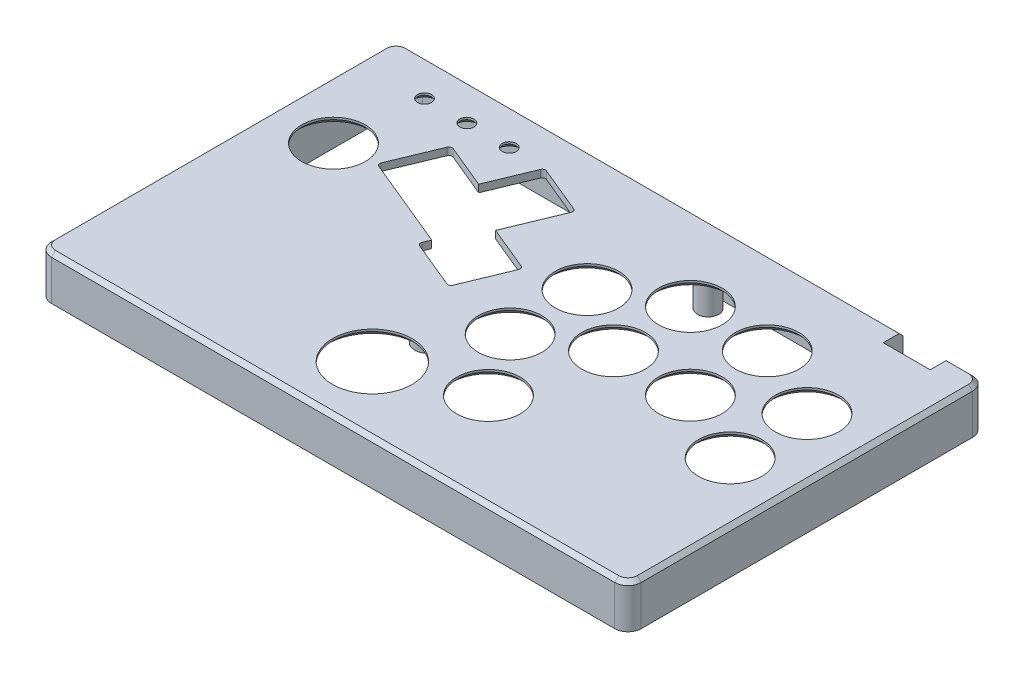
SolidWorks part; units mm, degrees
ref_plane "Front Plane" through (0, 0, 0) normal (0, 0, 1) x (1, 0, 0)
ref_plane "Top Plane" through (0, 0, 0) normal (0, 1, 0) x (1, 0, 0)
ref_plane "Right Plane" through (0, 0, 0) normal (1, 0, 0) x (0, 0, -1)
sketch "Sketch1" plane through (0, 0, 0) normal (0, 1, 0) x (1, 0, 0)
  line L1 (0, 0) -> (222.53, 0)
  line L2 (0, 0) -> (0, 135)
  line L3 (0, 135) -> (222.53, 135)
  line L4 (222.53, 0) -> (222.53, 135)
  dimension "D1" = 222.53
  dimension "D2" = 135
extrude "Top Plate" add sketch "Sketch1" along normal blind 16.6
fillet "Corner Fillet" radius 5 4 edges at (0, 8.3, -135) (0, 8.3, 0) (222.53, 8.3, -135) (222.53, 8.3, 0)
sketch "Sketch4" plane through (0, 16.6, 0) normal (0, -1, 0) x (-1, 0, 0)
  line L0 (-90.2544, 65.5244) -> (-72.6545, 72.8146) construction
  line L1 (-90.2544, 65.5244) -> (-97.5446, 83.1243) construction
  line L2 (-72.6545, 72.8146) -> (-74.1853, 76.5101) construction
  line L3 (-97.5446, 83.1243) -> (-79.9446, 90.4145) construction
  line L4 (-90.2544, 65.5244) -> (-79.9446, 90.4145) construction
  line L5 (-72.6545, 72.8146) -> (-97.5446, 83.1243) construction
  line L6 (-74.1853, 76.5101) -> (-56.5854, 83.8002) construction
  line L7 (-79.9446, 90.4145) -> (-81.4754, 94.11) construction
  line L8 (-56.5854, 83.8002) -> (-63.8755, 101.4001) construction
  line L9 (-81.4754, 94.11) -> (-63.8755, 101.4001) construction
  line L10 (-74.1853, 76.5101) -> (-63.8755, 101.4001) construction
  line L11 (-56.5854, 83.8002) -> (-81.4754, 94.11) construction
  line L12 (-56.5854, 83.8002) -> (-38.9854, 91.0903) construction
  line L14 (-38.9854, 91.0903) -> (-46.2756, 108.6902) construction
  line L15 (-63.8755, 101.4001) -> (-46.2756, 108.6902) construction
  line L16 (-56.5854, 83.8002) -> (-46.2756, 108.6902) construction
  line L17 (-38.9854, 91.0903) -> (-63.8755, 101.4001) construction
  line L19 (-63.8755, 101.4001) -> (-71.1656, 119) construction
  line L20 (-81.4754, 94.11) -> (-88.7655, 111.7099) construction
  line L21 (-71.1656, 119) -> (-88.7655, 111.7099) construction
  line L22 (-63.8755, 101.4001) -> (-88.7655, 111.7099) construction
  line L23 (-81.4754, 94.11) -> (-71.1656, 119) construction
  line L24 (-5, 0) -> (-217.53, 0) construction
  line L25 (-56.1261, 82.6915) -> (-38.5262, 89.9817)
  line L26 (-37.8768, 91.5495) -> (-45.1669, 109.1494)
  line L27 (-63.226, 102.968) -> (-46.7348, 109.7989)
  line L28 (-63.226, 102.968) -> (-70.0569, 119.4592)
  line L29 (-71.6248, 120.1087) -> (-89.2247, 112.8185)
  line L30 (-82.584, 93.6508) -> (-89.8742, 111.2507)
  line L31 (-81.5125, 91.0639) -> (-82.584, 93.6508)
  line L32 (-98.0038, 84.233) -> (-81.5125, 91.0639)
  line L33 (-91.3631, 65.0652) -> (-98.6532, 82.6651)
  line L34 (-89.7952, 64.4158) -> (-72.1953, 71.7059)
  line L35 (-71.5459, 73.2738) -> (-72.6174, 75.8606)
  line L36 (-72.6174, 75.8606) -> (-56.1261, 82.6915)
  line L37 (-62.7668, 101.8593) -> (-70.5162, 120.5679) construction
  line L38 (-64.3347, 102.5088) -> (-45.6261, 110.2581) construction
  line L39 (-70.5162, 120.5679) -> (-90.3334, 112.3593) construction
  line L40 (-82.584, 93.6508) -> (-90.3334, 112.3593) construction
  line L41 (-99.1124, 83.7738) -> (-81.5125, 91.0639) construction
  line L42 (-90.9039, 63.9566) -> (-99.1124, 83.7738) construction
  line L43 (-90.9039, 63.9566) -> (-71.0867, 72.1651) construction
  line L44 (-71.0867, 72.1651) -> (-72.6174, 75.8606) construction
  line L45 (-56.1261, 82.6915) -> (-37.4176, 90.4409) construction
  line L46 (-37.4176, 90.4409) -> (-45.6261, 110.2581) construction
  line L47 (-212.0995, 89.9694) -> (-222.53, 89.9694) construction
  line L50 (-118.0995, 88.9694) -> (-118.0995, 59.9694) construction
  line L51 (-143.0995, 102.9694) -> (-143.0995, 73.9694) construction
  line L52 (-172.0995, 102.9694) -> (-172.0995, 73.9694) construction
  line L53 (-200.0995, 89.9694) -> (-200.0995, 60.9694) construction
  line L54 (-217.53, 135) -> (-5, 135) construction
  line L55 (-222.53, 5) -> (-222.53, 130) construction
  line L56 (-10.4305, 88.9777) -> (0, 88.9777) construction
  line L57 (0, 130) -> (0, 5) construction
  line L58 (-118.0995, 30.9694) -> (-118.0995, 59.9694) construction
  line L59 (-118.0995, 59.9694) -> (-134.0995, 35.7827) construction
  circle A0 centre (-22.4305, 88.9777) radius 12
  circle A1 centre (-118.0995, 59.9694) radius 12
  circle A2 centre (-143.0995, 73.9694) radius 12
  circle A3 centre (-172.0995, 73.9694) radius 12
  circle A4 centre (-172.0995, 102.9694) radius 12
  circle A5 centre (-143.0995, 102.9694) radius 12
  circle A6 centre (-118.0995, 88.9694) radius 12
  arc A9 (-89.2247, 112.8185) -> (-89.8742, 111.2507) centre (-88.7655, 111.7099) ccw
  arc A10 (-98.0038, 84.233) -> (-98.6532, 82.6651) centre (-97.5446, 83.1243) ccw
  arc A11 (-91.3631, 65.0652) -> (-89.7952, 64.4158) centre (-90.2544, 65.5244) ccw
  arc A12 (-72.1953, 71.7059) -> (-71.5459, 73.2738) centre (-72.6545, 72.8146) ccw
  arc A13 (-38.5262, 89.9817) -> (-37.8768, 91.5495) centre (-38.9854, 91.0903) ccw
  arc A14 (-70.0569, 119.4592) -> (-71.6248, 120.1087) centre (-71.1656, 119) ccw
  arc A15 (-45.1669, 109.1494) -> (-46.7348, 109.7989) centre (-46.2756, 108.6902) ccw
  circle A18 centre (-200.0995, 89.9694) radius 12
  circle A19 centre (-200.0995, 60.9694) radius 12
  circle A20 centre (-101.0995, 24.9694) radius 15
  circle A21 centre (-134.0995, 35.7827) radius 12
  point P28 (-85.0995, 77.9694)
  point P29 (-69.0304, 88.9551)
  point P30 (-51.4305, 96.2452)
  point P35 (-76.3205, 106.555)
  dimension "D1" = 24
  dimension "D2" = 24
  dimension "D6" = 1.2
  dimension "D8" = 16
  dimension "D12" = 29
  dimension "D18" = 16
  dimension "D21" = 30
  dimension "D22" = 29
  dimension "D3" = 22.5
  dimension "D4" = 19.05
  dimension "D5" = 1.2
  dimension "D7" = 53
  dimension "D9" = 29
  dimension "D10" = 7.2675
  dimension "D11" = 4
  dimension "D13" = 25
  dimension "D14" = 29
  dimension "D15" = 14
  dimension "D16" = 13
  dimension "D17" = 28
  dimension "D19" = 18
  dimension "D20" = 33
  dimension "D23" = 16
extrude "Primary Buttons" cut sketch "Sketch4" along normal blind 10 contours A15 L26 A13 L25 L36 L35 A12 L34 A11 L33 A10 L32 L31 L30 A9 L29 A14 L28 L27 | A0 | A5 | A4 | A6 | A1 | A2 | A3 | A18 | A19 | A20 | A18 | A19 | A21 region at (70.5492, 16.6, -92.4849) region at (22.4305, 16.6, -88.9777) region at (118.0995, 16.6, -59.9694) region at (143.0995, 16.6, -73.9694) region at (172.0995, 16.6, -73.9694) region at (172.0995, 16.6, -102.9694) region at (143.0995, 16.6, -102.9694) region at (118.0995, 16.6, -88.9694) region at (200.0995, 16.6, -89.9694) region at (200.0995, 16.6, -60.9694) region at (101.0995, 16.6, -24.9694)
sketch "Sketch8" plane through (0, 0, 0) normal (0, -1, 0) x (1, 0, 0)
  line L24 (215.03, -127.5) -> (215.03, -7.5)
  line L25 (7.5, -127.5) -> (215.03, -127.5)
  line L26 (7.5, -7.5) -> (7.5, -127.5)
  line L27 (215.03, -7.5) -> (7.5, -7.5)
  line L28 (215.03, -127.5) -> (215.03, -7.5)
  line L29 (7.5, -127.5) -> (215.03, -127.5)
  line L30 (7.5, -7.5) -> (7.5, -127.5)
  line L31 (215.03, -7.5) -> (7.5, -7.5)
  dimension "D1" = 7.5
extrude "Hollow Out" cut sketch "Sketch8" against normal blind 13.8
sketch "Sketch24" plane through (0, 16.6, 0) normal (0, -1, 0) x (1, 0, 0)
  line L0 (143.0995, -73.9694) -> (172.0995, -73.9694) construction
  line L2 (157.5995, -56.1789) -> (157.5995, -73.9694) construction
  line L4 (95.6205, -51.4484) -> (106.8787, -55.716) construction
  line L6 (95.6205, -51.4484) -> (98.0601, -39.6583) construction
  line L8 (106.8787, -55.716) -> (118.0995, -59.9694) construction
  line L9 (98.0601, -39.6583) -> (101.0995, -24.9694) construction
  line L10 (80.4248, -116.4636) -> (59.6759, -66.3714) construction
  line L15 (71.6248, -120.1087) -> (89.2247, -112.8185) construction
  circle A1 centre (95.6205, -51.4484) radius 5
  circle A2 centre (157.5995, -56.1789) radius 5
  circle A4 centre (143.0995, -73.9694) radius 12 construction
  circle A5 centre (118.0995, -59.9694) radius 12 construction
  circle A6 centre (101.0995, -24.9694) radius 15 construction
  circle A7 centre (59.6759, -66.3714) radius 5
  dimension "D1" = 10
extrude "PCB Standoff" add sketch "Sketch24" along normal blind 9.8
sketch "Sketch31" plane through (0, 13.8, 0) normal (0, -1, 0) x (-1, 0, 0)
  line L0 (-7.5, 127.5) -> (-215.03, 127.5) construction
  line L1 (-90.265, 120.5) -> (-132.265, 120.5) construction
  line L2 (-132.265, 120.5) -> (-111.265, 120.5) construction
  line L3 (-111.265, 120.5) -> (-111.265, 135) construction
  line L5 (-217.53, 135) -> (-5, 135) construction
  circle A0 centre (-132.265, 120.5) radius 4
  circle A1 centre (-90.265, 120.5) radius 4
  dimension "D1" = 8
  dimension "D2" = 8
  dimension "D3" = 7
  dimension "D4" = 42
extrude "PCB Standoff 2" add sketch "Sketch31" along normal blind 12
hole_wizard "M3 Clearance Hole1" positions "3DSketch1" profile "Sketch3" hole size "M3" standard "ANSI Metric"
sketch3d "3DSketch1"
  line L4 (157.5995, 6.8, -56.1789) -> (157.5995, 13.8, -56.1789) construction
  line L5 (95.6205, 6.8, -51.4484) -> (95.6205, 13.8, -51.4484) construction
  circle A0 centre (59.6759, 6.8, -66.3714) radius 5 construction
  point P19 (157.5995, 6.8, -56.1789)
  point P23 (95.6205, 6.8, -51.4484)
  point P27 (59.6759, 6.8, -66.3714)
  point P33 (59.6759, 1.8, -66.3714)
sketch "Sketch3" plane through (157.5995, 6.8, -56.1789) normal (1, 0, 0) x (0, 0, -1)
  line L0 (0, 0) -> (0, 6.25)
  line L1 (0, 6.25) -> (1.7, 5.2285)
  line L2 (1.7, 5.2285) -> (1.7, 0)
  line L5 (1.7, 0) -> (0, 0)
  line L10 (0, 6.25) -> (-1.7, 5.2285) construction
  line L11 (0, -6.35) -> (0, 107.95) construction
  dimension "Hole Dia." = 3.4
  dimension "Hole Depth" = 6.25
  dimension "Drill Angle" = 118
hole_wizard "M3 Clearance Hole2" positions "3DSketch3" profile "Sketch32" hole size "M3" standard "ANSI Metric"
sketch3d "3DSketch3"
  line L1 (5, 0, 0) -> (217.53, 0, 0) construction
  line L2 (0, 0, -130) -> (0, 0, -5) construction
  line L5 (222.53, 0, -5) -> (222.53, 0, -130) construction
  line L6 (217.53, 0, -135) -> (5, 0, -135) construction
  point P0 (5.5, 0, -5.5)
  point P2 (217.03, 0, -5.5)
  point P4 (5.5, 0, -129.5)
  point P6 (217.03, 0, -129.5)
  dimension "D1" = 5.5
  dimension "D3" = 5.5
  dimension "D2" = 5.5
  dimension "D4" = 5.5
sketch "Sketch32" plane through (5.5, 0, -5.5) normal (1, 0, 0) x (0, 0, -1)
  line L0 (0, 0) -> (0, 14.25)
  line L1 (0, 14.25) -> (1.7, 13.2285)
  line L2 (1.7, 13.2285) -> (1.7, 0)
  line L5 (1.7, 0) -> (0, 0)
  line L10 (0, 14.25) -> (-1.7, 13.2285) construction
  line L11 (0, -6.35) -> (0, 107.95) construction
  dimension "Hole Dia." = 3.4
  dimension "Hole Depth" = 14.25
  dimension "Drill Angle" = 118
fillet "Fillet1" radius 10 3 edges at (7.5, 6.9, -127.5) (7.5, 6.9, -7.5) (215.03, 6.9, -7.5)
fillet "Fillet2" radius 5 1 edges at (215.03, 6.9, -127.5)
sketch "Sketch9" plane through (0, 16.6, 0) normal (0, 1, 0) x (1, 0, 0)
  line L0 (31.885, 115) -> (24.115, 115) construction
  line L3 (24.115, 115) -> (31.885, 115) construction
  line L4 (24.115, 119) -> (31.885, 119)
  line L5 (24.115, 111) -> (31.885, 111)
  line L6 (217.53, 135) -> (5, 135) construction
  line L7 (0, 130) -> (0, 5) construction
  arc A0 (24.115, 119) -> (24.115, 111) centre (24.115, 115) ccw
  arc A1 (31.885, 111) -> (31.885, 119) centre (31.885, 115) ccw
  point P8 (28, 115)
  dimension "D2" = 4
  dimension "D1" = 7.77
  dimension "D3" = 20
  dimension "D4" = 28
extrude "Light Guide Cutout" [suppressed] cut sketch "Sketch9" against normal blind 10
chamfer "Chamfer1" [suppressed] distance 1 angle 45
chamfer "Top Chamfer" distance 1.5 angle 45 8 edges at (221.0655, 16.6, -133.5355) (222.53, 16.6, -67.5) (221.0655, 16.6, -1.4645) (111.265, 16.6, -135) (1.4645, 16.6, -133.5355) (0, 16.6, -67.5) (1.4645, 16.6, -1.4645) (111.265, 16.6, 0)
sketch "Sketch11" plane through (0, 0, 0) normal (0, -1, 0) x (1, 0, 0)
  line L0 (217.03, -133.6012) -> (212.9288, -129.5)
  line L1 (217.03, -133.6012) -> (221.1312, -129.5)
  line L2 (212.9288, -129.5) -> (217.03, -125.3988)
  line L3 (221.1312, -129.5) -> (217.03, -125.3988)
  line L4 (217.03, -133.6012) -> (217.03, -125.3988) construction
  line L5 (212.9288, -129.5) -> (221.1312, -129.5) construction
  line L6 (1.3988, -129.5) -> (5.5, -125.3988)
  line L7 (1.3988, -129.5) -> (5.5, -133.6012)
  line L8 (5.5, -125.3988) -> (9.6012, -129.5)
  line L9 (5.5, -133.6012) -> (9.6012, -129.5)
  line L10 (1.3988, -129.5) -> (9.6012, -129.5) construction
  line L11 (5.5, -125.3988) -> (5.5, -133.6012) construction
  line L12 (5.5, -9.6012) -> (1.3988, -5.5)
  line L13 (5.5, -9.6012) -> (9.6012, -5.5)
  line L14 (1.3988, -5.5) -> (5.5, -1.3988)
  line L15 (9.6012, -5.5) -> (5.5, -1.3988)
  line L16 (5.5, -9.6012) -> (5.5, -1.3988) construction
  line L17 (1.3988, -5.5) -> (9.6012, -5.5) construction
  line L18 (217.03, -9.6012) -> (212.9288, -5.5)
  line L19 (217.03, -9.6012) -> (221.1312, -5.5)
  line L20 (212.9288, -5.5) -> (217.03, -1.3988)
  line L21 (221.1312, -5.5) -> (217.03, -1.3988)
  line L22 (217.03, -9.6012) -> (217.03, -1.3988) construction
  line L23 (212.9288, -5.5) -> (221.1312, -5.5) construction
  line L24 (217.53, -135) -> (5, -135) construction
  line L26 (92.7205, -54.3484) -> (98.5205, -54.3484)
  line L27 (92.7205, -54.3484) -> (92.7205, -48.5484)
  line L28 (92.7205, -48.5484) -> (98.5205, -48.5484)
  line L29 (98.5205, -54.3484) -> (98.5205, -48.5484)
  line L30 (92.7205, -54.3484) -> (98.5205, -48.5484) construction
  line L31 (92.7205, -48.5484) -> (98.5205, -54.3484) construction
  line L32 (160.4995, -59.0789) -> (154.6995, -59.0789)
  line L33 (160.4995, -59.0789) -> (160.4995, -53.2789)
  line L34 (160.4995, -53.2789) -> (154.6995, -53.2789)
  line L35 (154.6995, -59.0789) -> (154.6995, -53.2789)
  line L36 (160.4995, -59.0789) -> (154.6995, -53.2789) construction
  line L37 (160.4995, -53.2789) -> (154.6995, -59.0789) construction
  line L38 (56.7759, -63.4714) -> (62.5759, -63.4714)
  line L39 (56.7759, -63.4714) -> (56.7759, -69.2714)
  line L40 (56.7759, -69.2714) -> (62.5759, -69.2714)
  line L41 (62.5759, -63.4714) -> (62.5759, -69.2714)
  line L42 (56.7759, -63.4714) -> (62.5759, -69.2714) construction
  line L43 (56.7759, -69.2714) -> (62.5759, -63.4714) construction
  circle A0 centre (157.5995, -56.1789) radius 5 construction
  point P0 (95.6205, -51.4484)
  point P1 (217.03, -129.5)
  point P2 (5.5, -129.5)
  point P3 (5.5, -5.5)
  point P8 (217.03, -5.5)
  point P32 (157.5995, -56.1789)
  point P37 (59.6759, -66.3714)
  dimension "D1" = 45
  dimension "D2" = 5.8
extrude "Nut Cutout" cut sketch "Sketch11" against normal blind 2 from offset 8.2 contours L13 L15 L14 L12 | L7 L9 L8 L6 | L1 L3 L2 L0 | L19 L21 L20 L18 region at (217.03, 0, -129.5) region at (5.5, 0, -129.5) region at (5.5, 0, -5.5) region at (217.03, 0, -5.5) offset against normal yes
extrude "Nut Cutout 2" cut sketch "Sketch11<3>" against normal blind 2 from offset 8 contours L26 L29 L28 L27 | L35 L32 L33 L34 | L39 L38 L41 L40 region at (95.6205, 0, -51.4484) region at (157.5995, 0, -56.1789) offset against normal yes
sketch "Sketch11<3>" plane through (0, 0, 0) normal (0, -1, 0) x (1, 0, 0) same geometry as "Sketch11"
sketch "Sketch22" plane through (0, 16.6, -138.1) normal (0, -1, 0) x (1, 0, 0)
  line L0 (22.35, 17.35) -> (7.5, 17.35) construction
  line L6 (7.5, 120.6) -> (7.5, 20.6) construction
  line L7 (25, 17.35) -> (41, 17.35) construction
  line L8 (41, 17.35) -> (57, 17.35) construction
  line L9 (217.53, 3.1) -> (5, 3.1) construction
  circle A0 centre (25, 17.35) radius 2.65
  circle A1 centre (41, 17.35) radius 2.65
  circle A2 centre (57, 17.35) radius 2.65
  dimension "D2" = 5.3
  dimension "D1" = 3
  dimension "D3" = 17.5
  dimension "D4" = 14.25
  dimension "D5" = 16
extrude "Extra Buttons" cut sketch "Sketch22" along normal up to next contours A0 | A1 | A2 region at (25, 16.6, -120.75) region at (41, 16.6, -120.75) region at (57, 16.6, -120.75)
sketch "Sketch27" plane through (0, 13.8, 0) normal (0, -1, 0) x (1, 0, 0)
  line L0 (17.5, -127.5) -> (210.03, -127.5) construction
  line L1 (17.5, -127.5) -> (64.5, -127.5)
  line L2 (17.5, -127.5) -> (17.5, -117.5)
  line L3 (17.5, -117.5) -> (64.5, -117.5)
  line L4 (64.5, -127.5) -> (64.5, -117.5)
  arc A0 (7.5, -117.5) -> (17.5, -127.5) centre (17.5, -117.5) ccw construction
  dimension "D1" = 10
  dimension "D2" = 47
extrude "Extra Button Top Clearance" [suppressed] cut sketch "Sketch27" against normal blind 1.5
sketch "Sketch16" plane through (0, 135, -135) normal (0, 0, 1) x (1, 0, 0)
  line L0 (221.03, -118.4) -> (217.53, -118.4) construction
  line L6 (207.53, -119.9) -> (192.83, -119.9)
  line L7 (207.53, -119.9) -> (207.53, -127.2)
  line L9 (207.53, -127.2) -> (192.83, -127.2)
  line L10 (192.83, -119.9) -> (192.83, -127.2)
  line L11 (217.53, -119.9) -> (217.53, -135) construction
  line L12 (192.83, -119.9) -> (207.53, -127.2) construction
  line L13 (207.53, -119.9) -> (192.83, -127.2) construction
  dimension "D1" = 14.7
  dimension "D2" = 7.3
  dimension "D3" = 8.8
  dimension "D4" = 10
extrude "USB Receptacle Cutout" [suppressed] cut sketch "Sketch16" along normal blind 13.75 from surface starting at face at (113.765, 6.9, -127.5)
sketch "Sketch25" plane through (0, 0, -127.5) normal (0, 0, 1) x (1, 0, 0)
  line L0 (192.83, 15.1) -> (207.53, 7.8) construction
  line L1 (191.33, 0) -> (209.03, 0)
  line L2 (191.33, 0) -> (191.33, 22.9)
  line L3 (191.33, 22.9) -> (209.03, 22.9)
  line L4 (209.03, 0) -> (209.03, 22.9)
  line L5 (191.33, 0) -> (209.03, 22.9) construction
  line L6 (191.33, 22.9) -> (209.03, 0) construction
  line L7 (192.83, 15.1) -> (192.83, 7.8) construction
  line L10 (217.53, 0) -> (5, 0) construction
  point P0 (200.18, 11.45)
  dimension "D1" = 1.5
extrude "Host USB Cutout" cut sketch "Sketch25" against normal up to next
chamfer "Button Chamfer" distance 2 angle 45 11 edges at (22.4305, 13.8, -100.9777) (101.0995, 13.8, -39.9694) (134.0995, 13.8, -47.7827) (200.0995, 13.8, -72.9694) (200.0995, 13.8, -101.9694) (172.0995, 13.8, -85.9694) (172.0995, 13.8, -114.9694) (143.0995, 13.8, -85.9694) (118.0995, 13.8, -71.9694) (118.0995, 13.8, -100.9694) (143.0995, 13.8, -114.9694)
sketch "Sketch28" plane through (0, 0, -135) normal (0, 0, -1) x (-1, 0, 0)
  line L0 (-111.265, -0.1) -> (-111.265, 0) construction
  line L1 (-114.265, -2) -> (-108.265, -2)
  line L4 (-111.265, 1.19) -> (-111.265, -0.1) construction
  line L5 (-115.765, -0.5) -> (-115.765, 0.3)
  line L6 (-114.265, 1.8) -> (-108.265, 1.8)
  line L7 (-106.765, -0.5) -> (-106.765, 0.3)
  line L8 (-115.765, -2) -> (-106.765, 1.8) construction
  line L9 (-115.765, 1.8) -> (-106.765, -2) construction
  line L10 (-191.33, 0) -> (-5, 0) construction
  line L11 (-5, 0) -> (-217.53, 0) construction
  line L12 (-94.265, 1.8) -> (-86.265, 1.8) construction
  arc A2 (-114.265, -2) -> (-115.765, -0.5) centre (-114.265, -0.5) cw
  arc A3 (-115.765, 0.3) -> (-114.265, 1.8) centre (-114.265, 0.3) cw
  arc A4 (-108.265, -2) -> (-106.765, -0.5) centre (-108.265, -0.5) ccw
  arc A5 (-108.265, 1.8) -> (-106.765, 0.3) centre (-108.265, 0.3) cw
  dimension "D1" = 1.5
  dimension "D2" = 3.8
  dimension "D3" = 9
  dimension "D4" = 1.29
extrude "USB C Cutout" cut sketch "Sketch28" against normal up to next
sketch "Sketch29" plane through (0, 0, 0) normal (0, -1, 0) x (1, 0, 0)
  line L0 (17.5, -127.5) -> (106.765, -127.5) construction
  line L1 (103.265, -127.5) -> (119.265, -127.5)
  line L2 (103.265, -127.5) -> (103.265, -129.1)
  line L3 (103.265, -129.1) -> (119.265, -129.1)
  line L4 (119.265, -127.5) -> (119.265, -129.1)
  line L5 (106.765, -135) -> (5, -135) construction
  line L6 (101.265, -135) -> (121.265, -135)
  line L7 (101.265, -135) -> (101.265, -130.3)
  line L8 (101.265, -130.3) -> (121.265, -130.3)
  line L9 (121.265, -135) -> (121.265, -130.3)
  line L10 (114.265, -127.5) -> (108.265, -127.5) construction
  point P12 (111.265, -129.1)
  point P13 (111.265, -130.3)
  point P16 (111.265, -127.5)
  point P17 (111.265, -127.5)
  dimension "D1" = 16
  dimension "D2" = 1.2
  dimension "D3" = 1.6
  dimension "D4" = 20
extrude "Cord Relief" cut sketch "Sketch29" against normal offset from surface (4.1 mm away) 2.3 up to face at (111.265, 1.8, -131.25)
fillet "Fillet3" radius 2 2 edges at (101.265, 2.05, -135) (121.265, 2.05, -135)
sketch "Sketch30" plane through (0, 13.8, 0) normal (0, -1, 0) x (1, 0, 0)
  line L0 (17.5, -127.5) -> (191.33, -127.5) construction
  line L1 (189.33, -127.5) -> (215.03, -127.5)
  line L2 (189.33, -127.5) -> (189.33, -122.5)
  line L3 (189.33, -122.5) -> (215.03, -122.5)
  line L4 (215.03, -127.5) -> (215.03, -122.5)
  line L5 (215.03, -122.5) -> (215.03, -17.5) construction
  line L6 (191.33, -135) -> (191.33, -127.5) construction
  dimension "D1" = 2
  dimension "D2" = 5
extrude "Host USB cover" add sketch "Sketch30" along normal blind 4
chamfer "Chamfer2" distance 2 angle 45 3 edges at (25, 13.8, -123.4) (41, 13.8, -123.4) (57, 13.8, -123.4)
equation "\"D4@Sketch28\"=3.16/2-0.29"
